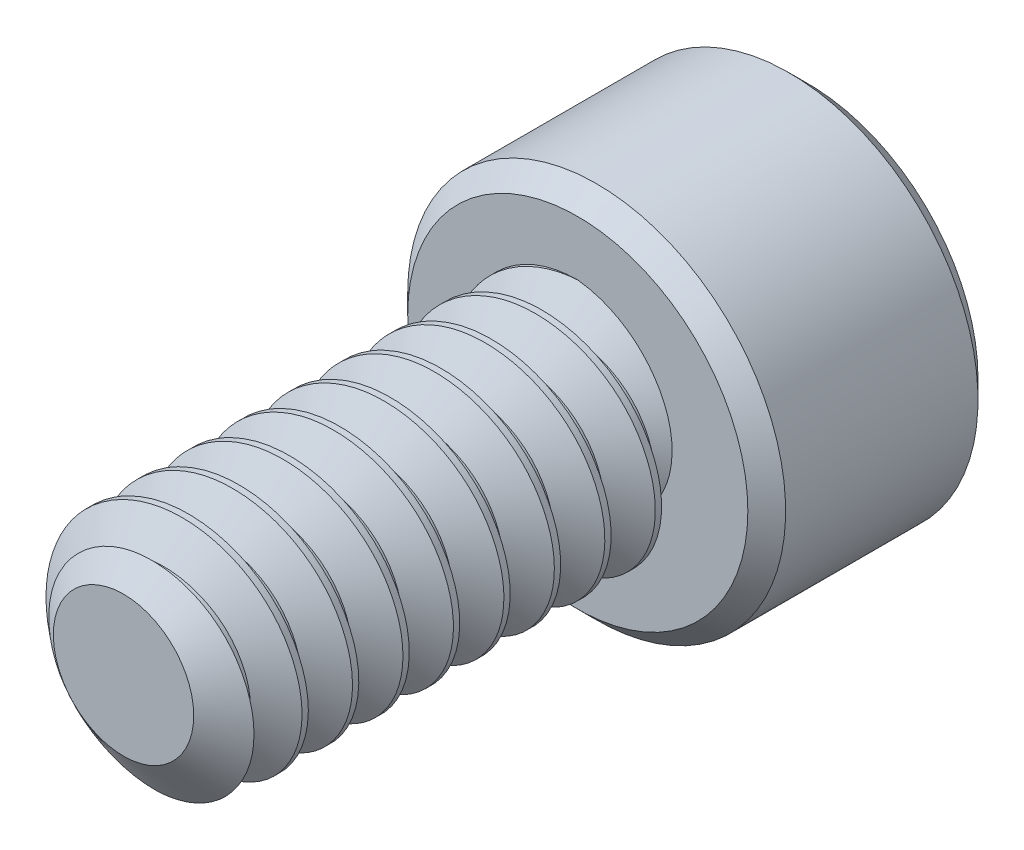
SolidWorks part; units mm, degrees
material "Alloy Steel"
ref_plane "Front Plane" through (0, 0, 0) normal (0, 0, 1) x (1, 0, 0)
ref_plane "Top Plane" through (0, 0, 0) normal (0, 1, 0) x (1, 0, 0)
ref_plane "Right Plane" through (0, 0, 0) normal (1, 0, 0) x (0, 0, -1)
sketch "Sketch1" plane through (0, 0, 0) normal (0, 0, 1) x (1, 0, 0)
  circle A0 centre (0, 0) radius 2.413
  dimension "OD" = 4.826
extrude "Extrude1" add sketch "Sketch1" against normal blind 9.525
sketch "Sketch2" plane through (0, 0, 0) normal (0, 0, 1) x (1, 0, 0)
  circle A0 centre (0, 0) radius 2.413 construction
  circle A1 centre (0, 0) radius 2.413
curve "Helix/Spiral1" pitch 1.0583 height 10.5833 turns 10 parameters "pitch"=1.0583
sketch "Sketch3" plane through (0, 0, 0) normal (1, 0, 0) x (0, 0, -1)
  line L0 (-0.926, 2.413) -> (-0.5292, 1.7256)
  line L1 (-0.5292, 1.7256) -> (-0.3969, 1.7256)
  line L2 (-0.3969, 1.7256) -> (0, 2.413)
  line L3 (-0.926, 2.413) -> (0, 2.413)
  line L4 (-0.463, 2.413) -> (-0.463, 1.7256) construction
  line L5 (-0.7276, 2.0693) -> (-0.1984, 2.0693) construction
  line L6 (0, 2.413) -> (0, -2.413) construction
  dimension "D1" = 0.1323
  dimension "D2" = 0.5292
  dimension "D3" = 60
sweep "Cut-Sweep1" cut profiles "Sketch3" path "Helix/Spiral1"
sketch "Sketch4" plane through (0, 0, 0) normal (1, 0, 0) x (0, 0, -1)
  line L0 (0.6592, 2.413) -> (0, 1.4716)
  line L1 (0, 1.4716) -> (0, 2.413)
  line L2 (0.6592, 2.413) -> (0, 2.413)
  line L3 (-0.926, 2.413) -> (0, 2.413) construction
  line L4 (0, 0) -> (7.0209, 0) construction
  dimension "D1" = 55
  dimension "D2" = 0.254
revolve "Cut-Revolve1" cut sketch "Sketch4" angle 360 about L4
sketch "Sketch5" plane through (0, 0, 0) normal (1, 0, 0) x (0, 0, -1)
  line L0 (9.525, -1.7471) -> (9.525, 1.7217) construction
  line L1 (9.525, 2.54) -> (15.9635, 2.54)
  line L2 (9.525, 2.54) -> (9.525, 0)
  line L3 (9.525, 0) -> (15.875, 0)
  line L4 (15.875, 2.2098) -> (15.875, 0)
  line L5 (15.9635, 2.54) -> (15.875, 2.2098)
  line L6 (0, 0) -> (9.9695, 0) construction
  point P3 (15.875, 2.54)
  point P10 (15.875, 2.54)
  dimension "D1" = 0.3302
  dimension "Thread min" = 15.875
  dimension "D2" = 0.127
  dimension "D3" = 15
revolve "partially thread" [suppressed] add sketch "Sketch5" angle 360 about L6
sketch "Sketch6" plane through (0, 0, -9.525) normal (0, 0, -1) x (-1, 0, 0)
  circle A0 centre (0, 0) radius 3.9624
  dimension "head dia" = 7.9248
extrude "Extrude2" add sketch "Sketch6" along normal blind 4.826
sketch "Sketch7" plane through (0, 0, -14.351) normal (0, 0, -1) x (-1, 0, 0)
  line L1 (0, 2.2914) -> (-1.9844, 1.1457)
  line L2 (-1.9844, 1.1457) -> (-1.9844, -1.1457)
  line L3 (-1.9844, -1.1457) -> (0, -2.2914)
  line L4 (0, -2.2914) -> (1.9844, -1.1457)
  line L5 (1.9844, -1.1457) -> (1.9844, 1.1457)
  line L6 (1.9844, 1.1457) -> (0, 2.2914)
  circle A0 centre (0, 0) radius 1.9844 construction
  dimension "hex dia" = 3.9688
extrude "Cut-Extrude1" cut sketch "Sketch7" against normal blind 2.9766
sketch "Sketch8" plane through (0, 0, -14.351) normal (0, 0, -1) x (-1, 0, 0)
  circle A0 centre (0, 0) radius 2.2914
extrude "Cut-Extrude2" cut sketch "Sketch8" against normal through all draft 45
chamfer "Chamfer1" distance 0.3962 angle 45 2 edges at (-3.9624, 0, -14.351) (-3.9624, 0, -9.525)
sketch "Sketch9" plane through (0, 0, 0) normal (1, 0, 0) x (0, 0, -1)
  line L0 (0, 2.413) -> (0, -2.413) construction
  line L1 (11.1125, 2.413) -> (11.1125, -2.413) construction
  dimension "D1" = 11.1125
  dimension "D4" = 0.635
  dimension "D5" = 0.3302
equation "\"D3@Helix/Spiral1\" = \"screw length@Extrude1\"+\"pitch@Helix/Spiral1\""
equation "\"D1@Sketch3\" = \"pitch@Helix/Spiral1\"*.125"
equation "\"D2@Sketch3\" = \"pitch@Helix/Spiral1\"*.5"
equation "\"D1@Cut-Extrude1\" = \"hex dia@Sketch7\"*.75"
equation "\"D1@Chamfer1\" = \"head dia@Sketch6\"*.05"
equation "\"D1@Sketch9\" = \"pitch@Helix/Spiral1\"*10.5"
